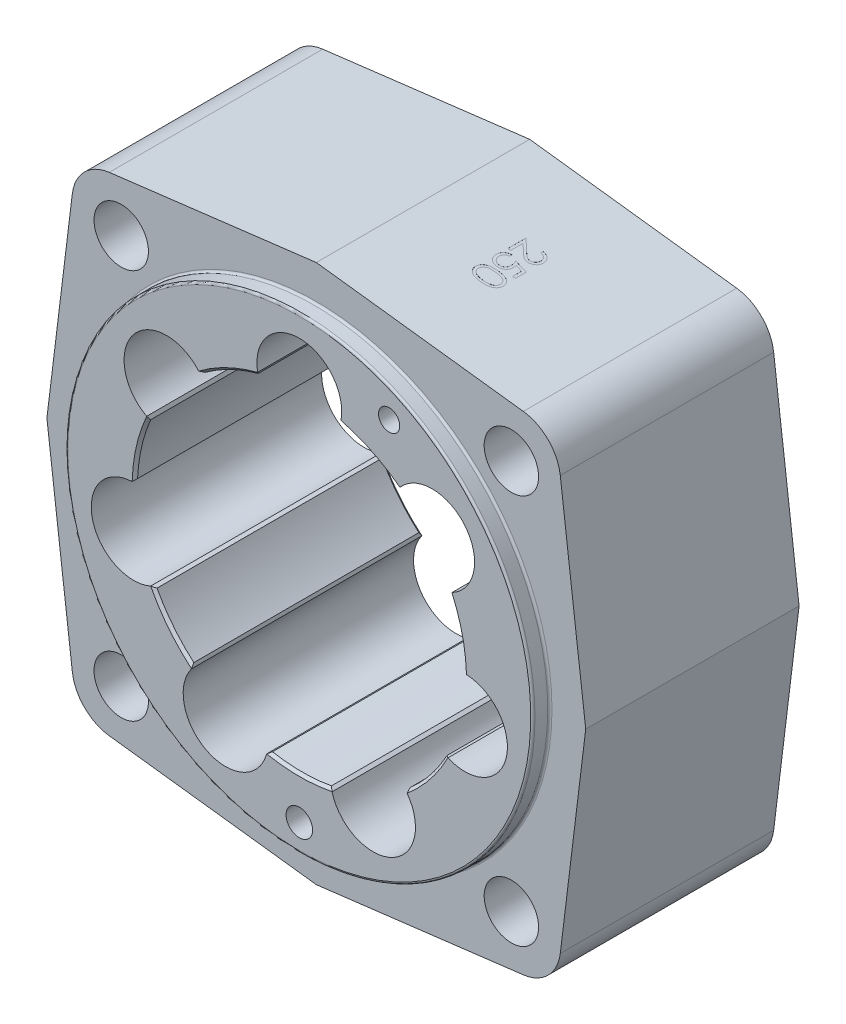
SolidWorks part; units mm, degrees
material "EN36A"
ref_plane "Front Plane" through (0, 0, 0) normal (0, 0, 1) x (1, 0, 0)
ref_plane "Top Plane" through (0, 0, 0) normal (0, 1, 0) x (1, 0, 0)
ref_plane "Right Plane" through (0, 0, 0) normal (1, 0, 0) x (0, 0, -1)
sketch "Sketch1" plane through (0, 0, 0) normal (0, 0, 1) x (1, 0, 0)
  line L0 (0, 0) -> (86.0326, 0) construction
  line L1 (0, 0) -> (0, 58.9688) construction
  line L2 (0, 50.75) -> (-38.9964, 45.9618)
  line L3 (0, 50.75) -> (38.9964, 45.9618)
  line L4 (45.9618, 38.9964) -> (50.75, 0)
  line L5 (45.9618, -38.9964) -> (50.75, 0)
  line L6 (-45.9618, -38.9964) -> (-50.75, 0)
  line L7 (-45.9618, 38.9964) -> (-50.75, 0)
  line L8 (0, -50.75) -> (38.9964, -45.9618)
  line L9 (0, -50.75) -> (-38.9964, -45.9618)
  arc A0 (-45.9618, 38.9964) -> (-38.9964, 45.9618) centre (-38.0215, 38.0215) cw
  arc A1 (-38.9964, -45.9618) -> (-45.9618, -38.9964) centre (-38.0215, -38.0215) cw
  arc A2 (45.9618, -38.9964) -> (38.9964, -45.9618) centre (38.0215, -38.0215) cw
  arc A3 (38.9964, 45.9618) -> (45.9618, 38.9964) centre (38.0215, 38.0215) cw
  circle A4 centre (0, 0) radius 31
  point P14 (-45.2001, 45.2001)
  point P17 (-45.2001, -45.2001)
  point P20 (45.2001, -45.2001)
  point P23 (45.2001, 45.2001)
  dimension "D5" = 8
  dimension "D6" = 62
  dimension "D1" = 166
  dimension "D2" = 166
  dimension "D3" = 101.5
  dimension "D4" = 101.5
extrude "Extrude1" add sketch "Sketch1" along normal mid plane 43.4
chamfer "Chamfer1" distance 0.5 angle 45 2 edges at (31, 0, -21.7) (31, 0, 21.7)
hole_wizard "Ø12.8 (12.8) Diameter Hole1" positions "Sketch3" profile "Sketch2" hole size "Ø12.8" standard "Ansi Metric"
sketch "Sketch3" plane through (0, 0, 21.7) normal (0, 0, 1) x (1, 0, 0)
  line L0 (0, 0) -> (0, 56.9426) construction
  line L1 (0, 0) -> (66.9225, 0) construction
  point P0 (-36.75, 36.75)
  point P1 (36.75, 36.75)
  point P3 (36.75, -36.75)
  point P5 (-36.75, -36.75)
  dimension "D1" = 73.5
  dimension "D2" = 73.5
sketch "Sketch2" plane through (-36.75, 36.75, 21.7) normal (1, 0, 0) x (0, -1, 0)
  line L0 (0, 0) -> (0, 319.0794)
  line L1 (0, 319.0794) -> (5.125, 316)
  line L2 (5.125, 316) -> (5.125, 0)
  line L5 (5.125, 0) -> (0, 0)
  line L10 (0, 319.0794) -> (-5.125, 316) construction
  line L11 (0, -6.35) -> (0, 107.95) construction
  dimension "Hole Dia." = 10.25
  dimension "Hole Depth" = 316
  dimension "Drill Angle" = 118
sketch "Sketch7" plane through (0, 0, 21.7) normal (0, 0, 1) x (1, 0, 0)
  circle A0 centre (0, 0) radius 71.34
  circle A1 centre (0, 0) radius 44
  dimension "D1" = 142.68
  dimension "D2" = 88
extrude "O-RING CUT" cut sketch "Sketch7" against normal blind 3.2
sketch "Sketch5" plane through (0, 0, 21.7) normal (0, 0, 1) x (1, 0, 0)
  line L0 (0, 0) -> (0, 54.7703) construction
  line L1 (1.3999, 0) -> (33.0817, 0) construction
  circle A0 centre (0, 32.01) radius 7.99
  dimension "D1" = 15.98
  dimension "D2" = 80
extrude "Extrude3" cut sketch "Sketch5" against normal up to next
pattern_circular "CirPattern1" count 7 over 360 about axis through (0, 0, 21.7) along (0, 0, -1) of "Extrude3"
sketch "Sketch6" plane through (0, 0, 21.7) normal (0, 0, 1) x (1, 0, 0)
  circle A0 centre (0, -39) radius 2.5
  dimension "D1" = 5
  dimension "D2" = 39
extrude "PIN HOLE" cut sketch "Sketch6" against normal up to next
fillet "Fillet1" radius 0.4 2 edges at (44, 0, 21.7) (44, 0, 18.5)
chamfer "Chamfer2" distance 0.5 angle 45 14 edges at (-30.988, 0.8641, 0) (-28.2941, 12.6667, 0) (-18.6451, 24.7661, 0) (-7.7379, 30.0187, 0) (18.6451, 24.7661, 0) (7.7379, 30.0187, 0) (30.988, 0.8641, 0) (28.2941, 12.6667, 0) (19.9962, -23.6886, 0) (27.5443, -14.2237, 0) (6.053, -30.4033, 0) (-6.053, -30.4033, 0) (-19.9962, -23.6886, 0) (-27.5443, -14.2237, 0) first distance on face at (-31.8178, -7.2622, 0) first distance on face at (-25.5159, 20.3483, 0) first distance on face at (0, 32.6361, 0) first distance on face at (25.5159, 20.3483, 0) first distance on face at (31.8178, -7.2622, 0) first distance on face at (14.1603, -29.4041, 0) first distance on face at (-14.1603, -29.4041, 0)
sketch "Sketch8" plane through (6.1388, 49.9963, 0) normal (-0.1219, -0.9925, 0) x (0, 0, -1)
  line L0 (-18.9, 7.954) -> (21.7, 7.954) construction
  line L1 (-18.9, -44) -> (-18.9, 44) construction
  line L2 (21.7, 33.1044) -> (21.7, -6.1849) construction
  text T0 "250" font "Century Gothic" height 5
extrude "Cut-Extrude1" cut sketch "Sketch8" along normal blind 0.01
hole_wizard "Ø4.0 (4) Diameter Hole1" positions "Sketch10" profile "Sketch9" hole size "Ø4.0" standard "Ansi Metric"
sketch "Sketch10" plane through (0, 0, 21.7) normal (0, 0, 1) x (1, 0, 0)
  line L0 (0, 0) -> (13.6673, 28.3805) construction
  arc A0 (18.946, 25.1654) -> (7.8625, 30.503) centre (0, 0) ccw construction
  point P0 (16.9215, 35.1378)
  dimension "D1" = 39
sketch "Sketch9" plane through (16.9215, 35.1378, 21.7) normal (1, 0, 0) x (0, -1, 0)
  line L0 (0, 0) -> (0, 7.2017)
  line L1 (0, 7.2017) -> (2, 6)
  line L2 (2, 6) -> (2, 0)
  line L5 (2, 0) -> (0, 0)
  line L10 (0, 7.2017) -> (-2, 6) construction
  line L11 (0, -6.35) -> (0, 107.95) construction
  dimension "Hole Dia." = 4
  dimension "Hole Depth" = 6
  dimension "Drill Angle" = 118
